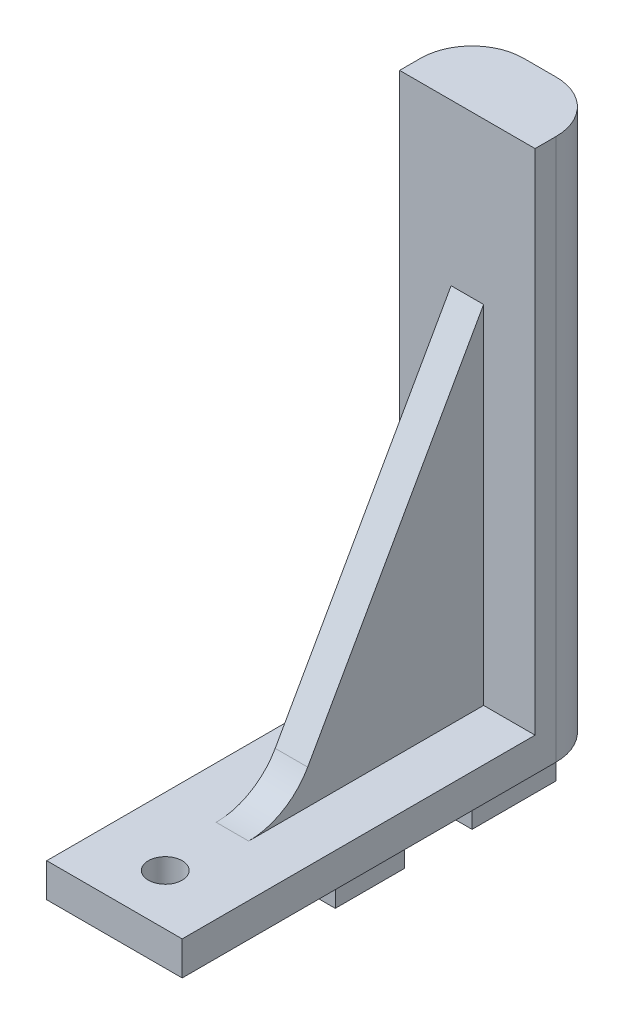
SolidWorks part; units mm, degrees
ref_plane "Front Plane" through (0, 0, 0) normal (0, 0, 1) x (1, 0, 0)
ref_plane "Top Plane" through (0, 0, 0) normal (0, 1, 0) x (1, 0, 0)
ref_plane "Right Plane" through (0, 0, 0) normal (1, 0, 0) x (0, 0, -1)
sketch "Sketch1" plane through (0, 0, 0) normal (1, 0, 0) x (0, 0, -1)
  line L0 (-19.939, 0) -> (19.939, 0)
  line L1 (19.939, 0) -> (19.939, 50.8)
  line L2 (19.939, 50.8) -> (13.1445, 50.8)
  line L3 (-19.939, 0) -> (-19.939, 3.175)
  line L5 (19.939, 0) -> (12.065, 0)
  line L6 (19.939, 0) -> (19.939, -6.35)
  line L7 (19.939, -6.35) -> (12.065, -6.35)
  line L8 (12.065, 0) -> (12.065, -6.35)
  line L9 (-0.762, 0) -> (5.715, 0)
  line L10 (-0.762, 0) -> (-0.762, -6.35)
  line L11 (-0.762, -6.35) -> (5.715, -6.35)
  line L12 (5.715, 0) -> (5.715, -6.35)
  line L13 (-32.8982, 3.175) -> (-19.939, 3.175) construction
  line L14 (11.303, 23.2833) -> (11.303, 35.9833) construction
  line L15 (9.7155, 6.35) -> (12.8905, 6.35) construction
  line L16 (9.7155, 6.35) -> (9.7155, 23.2833) construction
  line L17 (9.7155, 23.2833) -> (12.8905, 23.2833) construction
  line L18 (12.8905, 6.35) -> (12.8905, 23.2833) construction
  line L19 (9.7155, 35.9833) -> (12.8905, 35.9833) construction
  line L20 (9.7155, 35.9833) -> (9.7155, 52.9167) construction
  line L21 (9.7155, 52.9167) -> (12.8905, 52.9167) construction
  line L22 (12.8905, 35.9833) -> (12.8905, 52.9167) construction
  line L27 (11.303, 52.9167) -> (11.303, 65.6167) construction
  line L28 (9.4615, 6.096) -> (9.4615, 23.5373)
  line L29 (9.4615, 23.5373) -> (13.1445, 23.5373)
  line L30 (13.1445, 6.096) -> (13.1445, 23.5373)
  line L31 (9.4615, 6.096) -> (13.1445, 6.096)
  line L32 (9.4615, 35.7293) -> (9.4615, 53.1707)
  line L33 (9.4615, 53.1707) -> (13.1445, 53.1707)
  line L34 (13.1445, 35.7293) -> (13.1445, 53.1707)
  line L35 (9.4615, 35.7293) -> (13.1445, 35.7293)
  line L37 (13.1445, 50.8) -> (13.1445, 36.2585)
  line L38 (13.1445, 35.7293) -> (-5.1673, 3.175)
  line L39 (-5.1673, 3.175) -> (-19.939, 3.175)
  line L40 (9.4615, 23.5373) -> (6.2865, 23.5373) construction
  line L42 (9.4615, 6.096) -> (13.1445, 6.096)
  line L43 (9.4615, 6.096) -> (9.4615, 0)
  line L44 (9.4615, 0) -> (13.1445, 0)
  line L45 (13.1445, 6.096) -> (13.1445, 0)
  arc A2 (-19.939, 3.175) -> (13.1445, 36.2585) centre (-19.939, 36.2585) ccw
  point P8 (0, 0)
  point P16 (-15.1765, 0)
  dimension "D1" = 3.175
  dimension "D2" = 7.874
  dimension "D3" = 6.35
  dimension "D4" = 6.477
  dimension "D5" = 6.35
  dimension "D6" = 4.7625
  dimension "D7" = 14.4145
  dimension "D9" = 50.8
  dimension "D11" = 3.175
  dimension "D12" = 3.175
  dimension "D13" = 7.0485
  dimension "D14" = 6.35
  dimension "D15" = 12.7
  dimension "D16" = 16.9333
  dimension "D17" = 0.254
  dimension "D18" = 0.254
extrude "Boss-Extrude1" add sketch "Sketch1" along normal mid plane 12.7 contours A2 L38 L39 L3 L0 L43 L28 | L45 L31 L43 L0 | A2 L28 L31 L30 L29 | A2 L29 L30 L45 L5 L1 L2 L34 L38 | L38 A2 L28 L29 | L28 A2 L29 region at (0, 5.7443, -0.298) region at (0, 21.1823, -6.7645) region at (0, 3.048, -11.303) region at (0, 25.4385, -16.4178) region at (0, 14.6351, -11.3365) region at (0, 22.7069, -9.8482)
extrude "Boss-Extrude2" add sketch "Sketch1<3>" along normal mid plane 3.048 contours L0 L8 L7 L6 | L12 L0 L10 L11 region at (0, -3.175, -2.4765) region at (0, -3.175, -16.002)
sketch "Sketch1<3>" plane through (0, 0, 0) normal (1, 0, 0) x (0, 0, -1) same geometry as "Sketch1"
sketch "Sketch2" plane through (0, 0, 0) normal (0, -1, 0) x (1, 0, 0)
  circle A0 centre (0, 15.1765) radius 1.5875
  dimension "D1" = 3.175
extrude "Cut-Extrude1" cut sketch "Sketch2" against normal through all
fillet "Fillet1" radius 4.826 2 edges at (-6.35, 25.4, -19.939) (6.35, 25.4, -19.939)
fillet "Fillet2" radius 6.35 1 edges at (0, 3.175, 5.1673)
sketch "Sketch4" plane through (0, 50.8, 0) normal (0, 1, 0) x (1, 0, 0)
  line L0 (1.524, 19.939) -> (-1.524, 19.939) construction
  line L1 (-6.35, -19.939) -> (6.35, -19.939)
  line L2 (-6.35, -19.939) -> (-6.35, 19.939)
  line L3 (-6.35, 19.939) -> (6.35, 19.939)
  line L4 (6.35, -19.939) -> (6.35, 19.939)
  line L5 (-1.524, 19.939) -> (-1.524, 12.065) construction
  line L6 (1.524, 19.939) -> (-1.524, 19.939)
  line L7 (1.524, 19.939) -> (1.524, -19.939)
  line L8 (1.524, -19.939) -> (-1.524, -19.939)
  line L9 (-1.524, 19.939) -> (-1.524, -19.939)
  line M9 (-6.35, 13.1445) -> (6.35, 13.1445)
extrude "Cut-Extrude5" cut sketch "Sketch4" against normal up to surface (47.625 mm away) contours L9 L2 L1 M9 | L7 L1 L4 M9 region at (-3.937, 50.8, 3.3972) region at (3.937, 50.8, 3.3972) up to face at (0, 3.175, 13.589)
